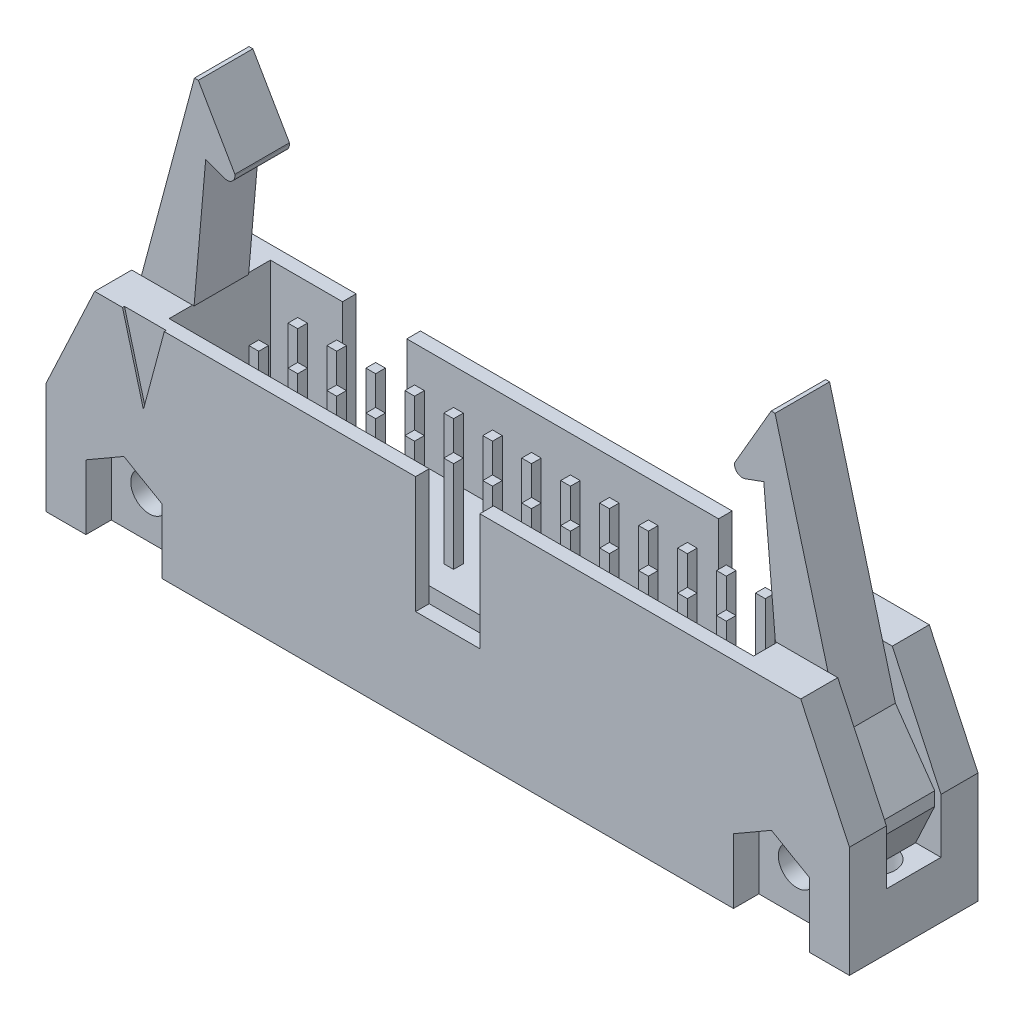
SolidWorks part; units mm, degrees
ref_plane "Front Plane" through (0, 0, 0) normal (0, 0, 1) x (1, 0, 0)
ref_plane "Top Plane" through (0, 0, 0) normal (0, 1, 0) x (1, 0, 0)
ref_plane "Right Plane" through (0, 0, 0) normal (1, 0, 0) x (0, 0, -1)
sketch "Sketch1" plane through (0, 0, 0) normal (0, 0, 1) x (1, 0, 0)
  line L1 (0, 0) -> (52.3748, 0)
  line L2 (0, 0) -> (0, 14.0208)
  line L3 (0, 14.0208) -> (52.3748, 14.0208)
  line L4 (52.3748, 0) -> (52.3748, 14.0208)
  dimension "D1" = 52.3748
  dimension "D2" = 14.0208
extrude "Base-Extrude" add sketch "Sketch1" against normal blind 8.382
sketch "Sketch2" plane through (0, 0, 0) normal (0, 0, 1) x (1, 0, 0)
  line L0 (26.1874, 14.0208) -> (26.1874, 0) construction
  line L1 (52.3748, 14.0208) -> (0, 14.0208) construction
  line L2 (0, 0) -> (52.3748, 0) construction
  line L3 (3.175, 14.0208) -> (0, 7.239)
  line L4 (0, 14.0208) -> (0, 0) construction
  line L5 (0, 14.0208) -> (0, 7.239)
  line L6 (0, 14.0208) -> (3.175, 14.0208)
  line L7 (52.3748, 14.0208) -> (49.1998, 14.0208)
  line L8 (52.3748, 14.0208) -> (52.3748, 7.239)
  line L9 (49.1998, 14.0208) -> (52.3748, 7.239)
  dimension "D1" = 7.239
  dimension "D2" = 3.175
extrude "Angle Cut Outside" cut sketch "Sketch2" against normal through all
sketch "Sketch3" plane through (0, 14.0208, 0) normal (0, 1, 0) x (-1, 0, 0)
  line L4 (-3.175, -4.191) -> (-49.1998, -4.191) construction
  line L5 (-3.175, -8.382) -> (-3.175, 0) construction
  line L6 (-49.1998, -8.382) -> (-49.1998, 0) construction
  line L7 (-26.1874, 0) -> (-26.1874, -8.382) construction
  line L8 (-49.1998, 0) -> (-3.175, 0) construction
  line L9 (-49.1998, -8.382) -> (-3.175, -8.382) construction
  line L10 (-7.1374, -7.493) -> (-7.1374, -0.889)
  line L11 (-7.1374, -0.889) -> (-45.2374, -0.889)
  line L12 (-45.2374, -7.493) -> (-45.2374, -0.889)
  line L13 (-7.1374, -7.493) -> (-45.2374, -7.493)
  point P16 (-26.1874, -0.889)
  point P18 (-45.2374, -4.191)
  point P19 (-7.1374, -4.191)
  dimension "D1" = 3.302
  dimension "D2" = 19.05
extrude "Inside Cut1" cut sketch "Sketch3" against normal blind 6.604
sketch "Sketch4" plane through (0, 0, 0) normal (0, 0, 1) x (1, 0, 0)
  line L0 (26.1874, 0) -> (26.1874, 14.0208) construction
  line L1 (0, 0) -> (52.3748, 0) construction
  line L2 (49.1998, 14.0208) -> (3.175, 14.0208) construction
  line L3 (24.0919, 14.0208) -> (24.0919, 6.4008)
  line L4 (24.0919, 6.4008) -> (28.2829, 6.4008)
  line L5 (24.0919, 14.0208) -> (28.2829, 14.0208)
  line L6 (28.2829, 14.0208) -> (28.2829, 6.4008)
  point P11 (26.1874, 6.4008)
  dimension "D1" = 2.0955
  dimension "D2" = 7.62
extrude "Center Cut1" cut sketch "Sketch4" against normal blind 0.889
sketch "Sketch5" plane through (0, 7.4168, 0) normal (0, 1, 0) x (-1, 0, 0)
  line L0 (-26.1874, 0) -> (-26.1874, -8.382) construction
  line L1 (-24.0919, 0) -> (-28.2829, 0) construction
  line L2 (-49.1998, -8.382) -> (-3.175, -8.382) construction
  line L3 (0, -4.191) -> (-52.3748, -4.191) construction
  line L4 (0, -8.382) -> (0, 0) construction
  line L5 (-52.3748, -8.382) -> (-52.3748, 0) construction
  line L6 (-11.2649, -3.2385) -> (-10.6299, -2.6035) construction
  line L7 (-10.6299, -2.6035) -> (-11.2649, -2.6035)
  line L8 (-10.6299, -2.6035) -> (-10.6299, -3.2385)
  line L9 (-10.6299, -3.2385) -> (-11.2649, -3.2385)
  line L10 (-11.2649, -2.6035) -> (-11.2649, -3.2385)
  circle A0 centre (-10.9474, -2.921) radius 0.3175 construction
  dimension "D3" = 0.635
  dimension "D1" = 15.24
  dimension "D2" = 1.27
extrude "Pin 1 Boss" add sketch "Sketch5" along normal blind 5.969
pattern_linear "26p Pattern" count 13 spacing 2.54 along (1, 0, 0) count 2 spacing 2.54 along (0, 0, -1) of "Pin 1 Boss"
sketch "Sketch6" plane through (0, 0, -8.382) normal (0, 0, -1) x (-1, 0, 0)
  line L0 (-26.1874, 0) -> (-26.1874, 14.0208) construction
  line L1 (0, 0) -> (-52.3748, 0) construction
  line L2 (-49.1998, 14.0208) -> (-3.175, 14.0208) construction
  line L3 (-40.5384, 14.0208) -> (-40.5384, 6.4008)
  line L4 (-40.5384, 6.4008) -> (-36.3474, 6.4008)
  line L5 (-36.3474, 6.4008) -> (-36.3474, 14.0208)
  line L6 (-40.5384, 14.0208) -> (-36.3474, 14.0208)
  line L7 (-11.8364, 14.0208) -> (-16.0274, 14.0208)
  line L8 (-16.0274, 6.4008) -> (-16.0274, 14.0208)
  line L9 (-11.8364, 6.4008) -> (-16.0274, 6.4008)
  line L10 (-11.8364, 14.0208) -> (-11.8364, 6.4008)
  dimension "D1" = 4.191
  dimension "D2" = 10.16
  dimension "D3" = 7.62
extrude "Rear Cut1" cut sketch "Sketch6" against normal blind 0.889
ref_plane "Latch Plane" through (0, 0, -2.413) normal (0, 0, 1) x (1, 0, 0)
sketch "Sketch7" plane through (0, 0, -2.413) normal (0, 0, 1) x (1, 0, 0)
  line L0 (26.1874, 0) -> (26.1874, 14.0208) construction
  line L1 (0, 0) -> (52.3748, 0) construction
  line L2 (36.3474, 14.0208) -> (16.0274, 14.0208) construction
  line L3 (44.3791, 22.6702) -> (45.1358, 14.0208)
  line L4 (24.0919, 14.0208) -> (3.175, 14.0208) construction
  line L5 (7.239, 14.0208) -> (3.81, 14.0208)
  line L6 (3.81, 14.0208) -> (7.2614, 26.9014)
  line L7 (7.2614, 26.9014) -> (7.5154, 26.9014)
  line L8 (7.5154, 26.9014) -> (9.9007, 22.7878)
  line L9 (9.9007, 22.7878) -> (9.9007, 22.7024)
  line L10 (9.219, 22.225) -> (7.9957, 22.6702)
  line L11 (7.9957, 22.6702) -> (7.239, 14.0208)
  line L12 (43.1558, 22.225) -> (44.3791, 22.6702)
  line L13 (42.4741, 22.7878) -> (42.4741, 22.7024)
  line L14 (44.8594, 26.9014) -> (42.4741, 22.7878)
  line L15 (45.1134, 26.9014) -> (44.8594, 26.9014)
  line L16 (48.5648, 14.0208) -> (45.1134, 26.9014)
  line L17 (45.1358, 14.0208) -> (48.5648, 14.0208)
  arc A0 (9.219, 22.225) -> (9.9007, 22.7024) centre (9.3927, 22.7024) ccw
  arc A1 (43.1558, 22.225) -> (42.4741, 22.7024) centre (42.9821, 22.7024) cw
  dimension "D9" = 0.508
  dimension "D1" = 0.635
  dimension "D2" = 13.335
  dimension "D3" = 75
  dimension "D4" = 3.429
  dimension "D5" = 22.225
  dimension "D6" = 85
  dimension "D7" = 0.254
  dimension "D8" = 1.905
  dimension "D10" = 0.762
  dimension "D11" = 75
extrude "Latches" add sketch "Sketch7" against normal blind 3.556
sketch "Sketch8" plane through (0, 0, -2.413) normal (0, 0, 1) x (1, 0, 0)
  line L0 (7.2614, 26.9014) -> (3.81, 14.0208) construction
  line L1 (3.81, 14.0208) -> (2.9747, 10.9033)
  line L2 (26.1874, 0) -> (26.1874, 14.0208) construction
  line L3 (0, 0) -> (52.3748, 0) construction
  line L4 (24.0919, 14.0208) -> (3.175, 14.0208) construction
  line L5 (0.4089, 7.239) -> (2.9747, 10.9033)
  line L6 (0.4089, 7.239) -> (0.4089, 6.35)
  line L7 (1.6525, 3.683) -> (0, 3.683)
  line L8 (0, 7.239) -> (0, 0) construction
  line L9 (0.4089, 6.35) -> (1.6525, 3.683)
  line L10 (0, 7.239) -> (0, 3.683)
  line L11 (0, 7.239) -> (3.175, 14.0208) construction
  line L12 (0, 7.239) -> (3.175, 14.0208)
  line L13 (3.81, 14.0208) -> (3.175, 14.0208)
  line L14 (48.5648, 14.0208) -> (49.1998, 14.0208)
  line L15 (52.3748, 7.239) -> (49.1998, 14.0208)
  line L16 (52.3748, 7.239) -> (52.3748, 3.683)
  line L17 (51.9659, 6.35) -> (50.7223, 3.683)
  line L18 (50.7223, 3.683) -> (52.3748, 3.683)
  line L19 (51.9659, 7.239) -> (51.9659, 6.35)
  line L20 (51.9659, 7.239) -> (49.4001, 10.9033)
  line L21 (48.5648, 14.0208) -> (49.4001, 10.9033)
  dimension "D1" = 3.683
  dimension "D2" = 1.6525
  dimension "D3" = 6.35
  dimension "D4" = 65
  dimension "D5" = 160
extrude "Latch Cut1" cut sketch "Sketch8" against normal blind 3.556
sketch "Sketch9" plane through (0, 0, 0) normal (0, 0, 1) x (1, 0, 0)
  line L0 (4.9888, 14.0208) -> (6.35, 8.9408)
  line L1 (24.0919, 14.0208) -> (3.175, 14.0208) construction
  line L2 (6.35, 8.9408) -> (7.7112, 14.0208)
  line L3 (7.7112, 14.0208) -> (4.9888, 14.0208)
  line L4 (6.35, 14.0208) -> (6.35, 0) construction
  line L5 (0, 0) -> (52.3748, 0) construction
  dimension "D1" = 30
  dimension "D2" = 6.35
  dimension "D3" = 5.08
extrude "Pin 1 Triangle Cut" cut sketch "Sketch9" against normal blind 0.127
sketch "Sketch10" plane through (0, 0, 0) normal (0, 0, 1) x (1, 0, 0)
  line L0 (26.1874, 0) -> (26.1874, 14.0208) construction
  line L1 (0, 0) -> (52.3748, 0) construction
  line L2 (36.3474, 14.0208) -> (16.0274, 14.0208) construction
  line L3 (5.9524, 0.4381) -> (7.3994, 1.2735) [skipped]
  line L4 (2.271, 1.5562) -> (3.718, 0.7208) [skipped]
  line L5 (7.5565, 0) -> (7.5565, 4.2238)
  line L6 (7.5565, 4.2238) -> (5.08, 5.6536)
  line L7 (5.08, 5.6536) -> (2.6035, 4.2238)
  line L8 (2.6035, 4.2238) -> (2.6035, 0)
  line L9 (2.6035, 0) -> (7.5565, 0)
  line L10 (49.7713, 0) -> (44.8183, 0)
  line L11 (49.7713, 4.2238) -> (49.7713, 0)
  line L12 (47.2948, 5.6536) -> (49.7713, 4.2238)
  line L13 (44.8183, 4.2238) -> (47.2948, 5.6536)
  line L14 (44.8183, 0) -> (44.8183, 4.2238)
  circle A0 centre (5.08, 2.794) radius 2.4765 construction
  circle A1 centre (47.2948, 2.794) radius 2.4765 construction
  dimension "D1" = 4.953
  dimension "D2" = 2.794
  dimension "D3" = 5.08
  dimension "D4" = 21.1074
extrude "Screw Recess" cut sketch "Sketch10" against normal blind 1.651
sketch "Sketch12" plane through (0, 0, 0) normal (0, 0, 1) x (1, 0, 0)
  line L0 (26.1874, 0) -> (26.1874, 14.0208) construction
  line L1 (7.5565, 0) -> (44.8183, 0) construction
  line L2 (36.3474, 14.0208) -> (16.0274, 14.0208) construction
  circle A0 centre (5.08, 2.794) radius 1.2065
  circle A1 centre (47.2948, 2.794) radius 1.2065
  dimension "D1" = 2.413
extrude "Screw Hole" cut sketch "Sketch12" against normal through all
sketch "Sketch13" plane through (0, 0, 0) normal (0, -1, 0) x (1, 0, 0)
  line L0 (26.1874, -8.382) -> (26.1874, 0) construction
  line L1 (0, -8.382) -> (52.3748, -8.382) construction
  line L2 (7.5565, 0) -> (44.8183, 0) construction
  line L3 (0, -8.382) -> (0, 0) construction
  circle A0 centre (2.032, -3.7338) radius 1.27
  circle A1 centre (50.3428, -3.7338) radius 1.27
  dimension "D1" = 2.54
  dimension "D2" = 3.7338
  dimension "D3" = 2.032
  dimension "D4" = 24.1554
extrude "Vert Mnt Hole" cut sketch "Sketch13" against normal up to surface (3.683 mm away) up to face at (0.8263, 3.683, -4.191)
sketch "Sketch15" plane through (0, 0, -8.382) normal (0, 0, -1) x (-1, 0, 0)
  line L0 (-26.1874, 0) -> (-26.1874, 14.0208) construction
  line L1 (0, 0) -> (-52.3748, 0) construction
  line L2 (-36.3474, 14.0208) -> (-16.0274, 14.0208) construction
  line L3 (-8.9154, 0) -> (-8.9154, 4.318)
  line L4 (-8.9154, 4.318) -> (-43.4594, 4.318)
  line L5 (-43.4594, 0) -> (-8.9154, 0)
  line L6 (-43.4594, 0) -> (-43.4594, 4.318)
  point P10 (-26.1874, 4.318)
  dimension "D1" = 17.272
  dimension "D2" = 4.318
extrude "R Ang Rear Cut1" cut sketch "Sketch15" against normal blind 1.524
sketch "Sketch14" plane through (0, 0, -6.858) normal (0, 0, -1) x (-1, 0, 0)
  line L0 (-47.2948, 2.794) -> (-5.08, 2.794) construction
  line L1 (-26.1874, 2.794) -> (-26.1874, 14.0208) construction
  line L3 (-36.3474, 14.0208) -> (-16.0274, 14.0208) construction
  circle A0 centre (-10.9474, 0.9906) radius 0.4445
  dimension "D1" = 0.889
  dimension "D2" = 1.8034
  dimension "D3" = 15.24
extrude "R Ang Pin1" [suppressed] add sketch "Sketch14" along normal blind 4.318
pattern_linear "R Ang Pattern" [suppressed] count 13 spacing 2.54 count 2 spacing 2.54
